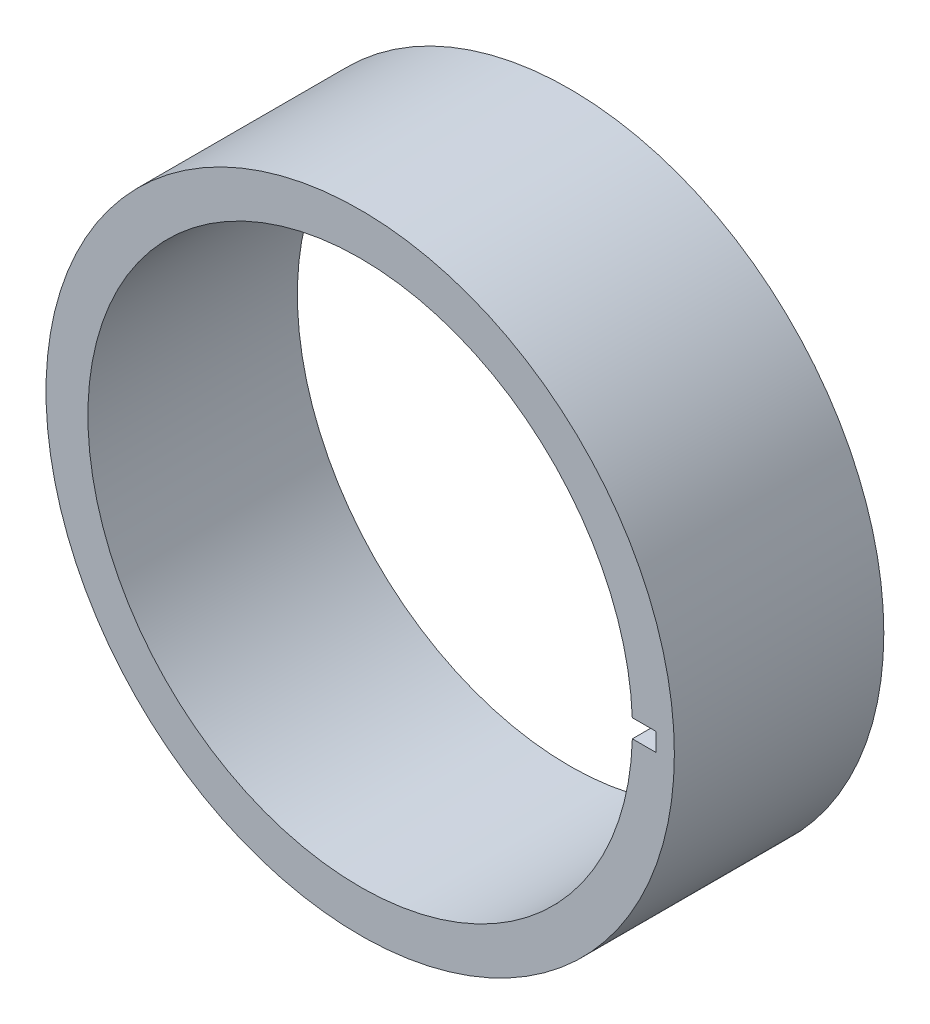
SolidWorks part; units mm, degrees
ref_plane "前视基准面" through (0, 0, 0) normal (0, 0, 1) x (1, 0, 0)
ref_plane "上视基准面" through (0, 0, 0) normal (0, 1, 0) x (1, 0, 0)
ref_plane "右视基准面" through (0, 0, 0) normal (1, 0, 0) x (0, 0, -1)
other "Configuration Table"
sketch "Sketch1" plane through (0, 0, 0) normal (0, 0, 1) x (1, 0, 0)
  circle A0 centre (0, 0) radius 60
  circle A1 centre (0, 0) radius 52
extrude "Boss-Extrude1" add sketch "Sketch1" along normal blind 20 and the other way blind 20
sketch "Sketch2" plane through (0, 0, 0) normal (0, 0, 1) x (1, 0, 0)
  line L0 (51.978, -1.5124) -> (56.4656, -1.5124)
  line L1 (56.4656, -1.5124) -> (56.4656, 1.9718)
  line L2 (56.4656, 1.9718) -> (51.9626, 1.9718)
  line L3 (51.9626, 1.9718) -> (51.978, -1.5124)
  circle A0 centre (0, 0) radius 52 construction
extrude "Cut-Extrude1" cut sketch "Sketch2" along normal blind 20 and the other way blind 20
sketch3d "3DSketch1"
  line L0 (0, 0, -10) -> (0, 0, 10) construction
ref_axis "central_axis" through (0, 0, -10) along (0, 0, 1)
ref_plane "mid_plane" through (0, 0, 0) normal (0, 0, 1) x (1, 0, 0)
